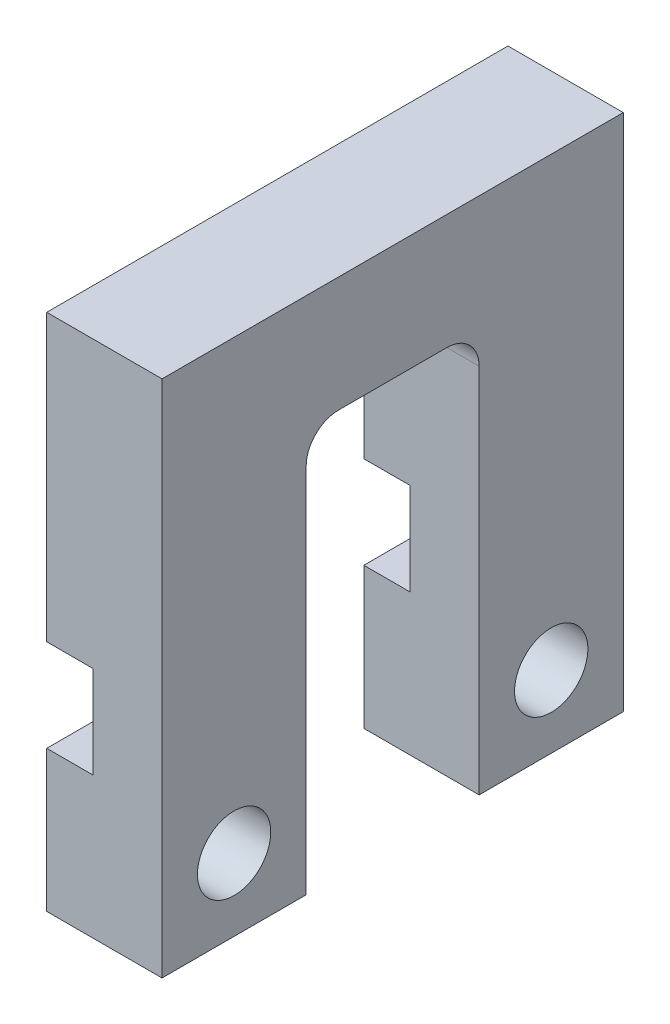
SolidWorks part; units mm, degrees
material "6061-T6 (SS)"
ref_plane "Front" through (0, 0, 0) normal (0, 0, 1) x (1, 0, 0)
ref_plane "Top" through (0, 0, 0) normal (0, 1, 0) x (1, 0, 0)
ref_plane "Right" through (0, 0, 0) normal (1, 0, 0) x (0, 0, -1)
sketch "Sketch1" plane through (0, 0, 0) normal (1, 0, 0) x (0, 0, -1)
  line L0 (7.9375, 0) -> (7.9375, 20.447)
  line L1 (0, 0) -> (7.9375, 0)
  line L2 (0, 0) -> (0, 28.575)
  line L3 (0, 28.575) -> (25.4, 28.575)
  line L4 (25.4, 0) -> (25.4, 28.575)
  line L5 (9.7155, 22.225) -> (15.6845, 22.225)
  line L6 (17.4625, 20.447) -> (17.4625, 0)
  line L7 (17.4625, 0) -> (25.4, 0)
  arc A0 (15.6845, 22.225) -> (17.4625, 20.447) centre (15.6845, 20.447) cw
  arc A1 (7.9375, 20.447) -> (9.7155, 22.225) centre (9.7155, 20.447) cw
  dimension "D5" = 1.778
  dimension "D1" = 28.575
  dimension "D2" = 25.4
  dimension "D3" = 22.225
  dimension "D4" = 9.525
extrude "Boss-Extrude1" add sketch "Sketch1" along normal blind 6.35
sketch "Sketch5" plane through (0, 0, 0) normal (-1, 0, 0) x (0, 0, 1)
  line L0 (-25.4, 0) -> (-21.4312, 3.9688) construction
  line L1 (-21.4312, 3.9688) -> (-17.4625, 0) construction
  line L4 (-7.9375, 0) -> (-3.9688, 3.9688) construction
  line L5 (-3.9688, 3.9688) -> (0, 0) construction
  point P0 (-21.4312, 3.9688)
  point P2 (-3.9688, 3.9688)
hole_wizard "#10-32 Tapped Hole1" positions "Sketch5" profile "Sketch4" tap size "#10-32" standard "ANSI Inch" end condition through all
sketch "Sketch4" plane through (0, 3.9688, -21.4312) normal (0, 1, 0) x (0, 0, 1)
  line L0 (0, 0) -> (0, 6.35)
  line L1 (0, 6.35) -> (2.0193, 6.35)
  line L2 (2.0193, 6.35) -> (2.0193, 0)
  line L5 (2.0193, 0) -> (0, 0)
  line L11 (0, -6.35) -> (0, 107.95) construction
  dimension "Thru Tap Drill Dia." = 4.0386
  dimension "Thru Tap Drill Depth" = 6.35
cosmetic thread "Hole Thread1" parameters "D2"=4.826
cosmetic thread "Hole Thread2" parameters "D2"=4.826
sketch "Sketch2" plane through (0, 0, 0) normal (-1, 0, 0) x (0, 0, 1)
  line L0 (-25.4, 0) -> (-25.4, 28.575) construction
  line L1 (-25.4, 7.7788) -> (0, 7.7788)
  line L2 (-25.4, 7.7788) -> (-25.4, 12.8588)
  line L3 (-25.4, 12.8588) -> (0, 12.8588)
  line L4 (0, 7.7788) -> (0, 12.8588)
  line L5 (0, 28.575) -> (0, 0) construction
  circle A0 centre (-3.9688, 3.9688) radius 2.0193 construction
  point P10 (0, 10.3188)
  dimension "D1" = 5.08
  dimension "D2" = 6.35
extrude "Cut-Extrude1" cut sketch "Sketch2" against normal blind 2.54
